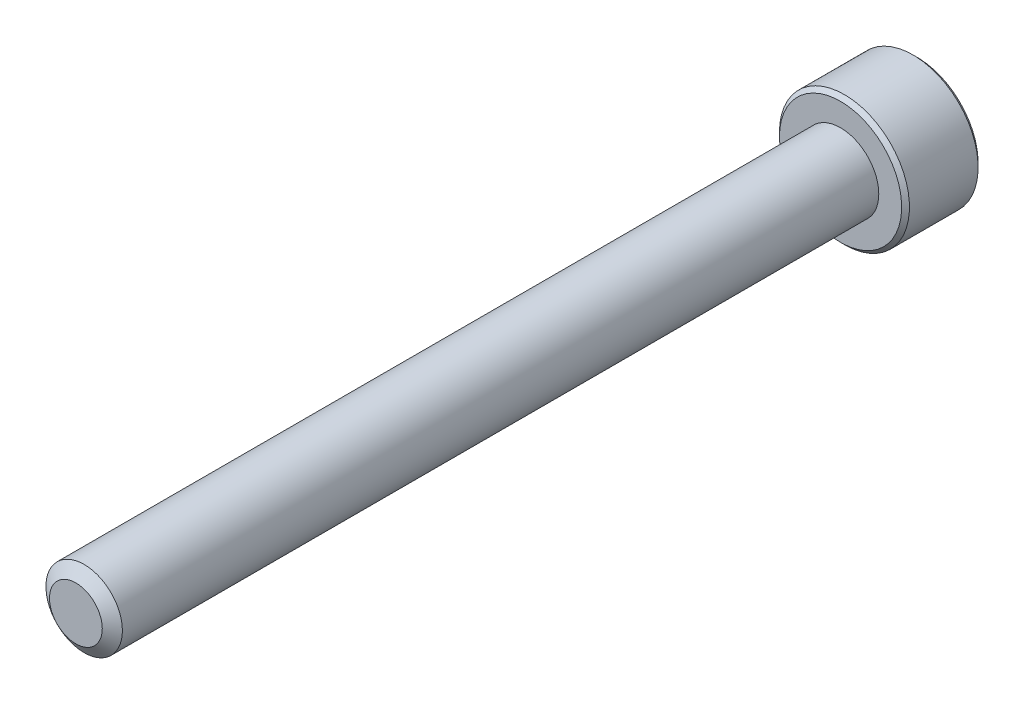
SolidWorks part; units mm, degrees
material "Alloy Steel"
ref_plane "Front Plane" through (0, 0, 0) normal (0, 0, 1) x (1, 0, 0)
ref_plane "Top Plane" through (0, 0, 0) normal (0, 1, 0) x (1, 0, 0)
ref_plane "Right Plane" through (0, 0, 0) normal (1, 0, 0) x (0, 0, -1)
sketch "Sketch1" plane through (0, 0, 0) normal (0, 0, 1) x (1, 0, 0)
  circle A0 centre (0, 0) radius 2.5
  dimension "OD" = 5
extrude "Extrude1" add sketch "Sketch1" against normal blind 50
sketch "Sketch2" plane through (0, 0, 0) normal (0, 0, 1) x (1, 0, 0)
  circle A0 centre (0, 0) radius 2.5 construction
  circle A1 centre (0, 0) radius 2.5
curve "Helix/Spiral1" [suppressed] pitch 0.8 height 50.8 turns 63.5 parameters "pitch"=0.8
sketch "Sketch3" plane through (0, 0, 0) normal (1, 0, 0) x (0, 0, -1)
  line L0 (-0.7, 2.5) -> (-0.4, 1.9804)
  line L1 (-0.4, 1.9804) -> (-0.3, 1.9804)
  line L2 (-0.3, 1.9804) -> (0, 2.5)
  line L3 (-0.7, 2.5) -> (0, 2.5)
  line L4 (-0.35, 2.5) -> (-0.35, 1.9804) construction
  line L5 (-0.55, 2.2402) -> (-0.15, 2.2402) construction
  line L6 (0, 2.5) -> (0, -2.5) construction
  line L7 (0, -2.5) -> (50, -2.5) construction
  point P11 (3.6, -2.5)
  dimension "D1" = 0.1
  dimension "D2" = 0.4
  dimension "D3" = 60
  dimension "D4" = 3.6
sweep "Cut-Sweep1" [suppressed] cut profiles "Sketch3" path "Helix/Spiral1"
sketch "Sketch4" plane through (0, 0, 0) normal (1, 0, 0) x (0, 0, -1)
  line L0 (0.5417, 2.5) -> (0, 1.7264)
  line L1 (0, 1.7264) -> (0, 2.5)
  line L2 (0.5417, 2.5) -> (0, 2.5)
  line L3 (-0.7, 2.5) -> (0, 2.5) construction
  line L4 (0, 0) -> (7.0209, 0) construction
  dimension "D1" = 55
  dimension "D2" = 0.254
revolve "Cut-Revolve1" cut sketch "Sketch4" angle 360 about L4
sketch "Sketch5" [suppressed] plane through (0, 0, 0) normal (1, 0, 0) x (0, 0, -1)
  line L0 (50, -1.7838) -> (50, 1.991) construction
  line L1 (50, 2.5) -> (22.1202, 2.5)
  line L2 (50, 2.5) -> (50, 0)
  line L3 (50, 0) -> (22, 0)
  line L4 (22, 2.1698) -> (22, 0)
  line L5 (22.1202, 2.5) -> (22, 2.1698)
  line L6 (0, 0) -> (9.9695, 0) construction
  point P3 (22, 2.5)
  point P10 (22, 2.5)
  dimension "D1" = 0.3302
  dimension "Thread min" = 22
  dimension "D3" = 20
revolve "partially thread" [suppressed] add sketch "Sketch5" angle 360 about L6
sketch "Sketch6" plane through (0, 0, -50) normal (0, 0, -1) x (-1, 0, 0)
  circle A0 centre (0, 0) radius 4.25
  dimension "head dia" = 8.5
extrude "Extrude2" add sketch "Sketch6" along normal blind 5
sketch "Sketch7" plane through (0, 0, -55) normal (0, 0, -1) x (-1, 0, 0)
  line L1 (0, 2.3094) -> (-2, 1.1547)
  line L2 (-2, 1.1547) -> (-2, -1.1547)
  line L3 (-2, -1.1547) -> (0, -2.3094)
  line L4 (0, -2.3094) -> (2, -1.1547)
  line L5 (2, -1.1547) -> (2, 1.1547)
  line L6 (2, 1.1547) -> (0, 2.3094)
  circle A0 centre (0, 0) radius 2 construction
  dimension "hex dia" = 4
extrude "Cut-Extrude1" cut sketch "Sketch7" against normal blind 3
sketch "Sketch8" plane through (0, 0, -55) normal (0, 0, -1) x (-1, 0, 0)
  circle A0 centre (0, 0) radius 2.3094
extrude "Cut-Extrude2" cut sketch "Sketch8" against normal through all draft 45
chamfer "Chamfer1" distance 0.255 angle 45 2 edges at (-4.25, 0, -55) (-4.25, 0, -50)
sketch "Sketch9" plane through (0, 0, 0) normal (1, 0, 0) x (0, 0, -1)
  line L0 (0, 2.5) -> (0, -2.5) construction
  line L1 (4.4, 2.5) -> (4.4, -2.5) construction
  dimension "D1" = 4.4
sketch "Sketch10" plane through (0, 0, 0) normal (1, 0, 0) x (0, 0, -1)
  line L0 (50, 2.5) -> (50, 0)
  line L1 (50, 2.5) -> (49.8, 2.5)
  line L2 (49.8, 2.5) -> (48.7645, 0)
  line L3 (50, 0) -> (48.7645, 0)
  line L4 (50, 3.995) -> (50, -3.995) construction
  dimension "D1" = 22.5
  dimension "D2" = 0.2
revolve "Revolve1" add sketch "Sketch10" angle 360 about L3
equation "\"D3@Helix/Spiral1\" = \"screw length@Extrude1\"+\"pitch@Helix/Spiral1\""
equation "\"D1@Sketch3\" = \"pitch@Helix/Spiral1\"*.125"
equation "\"D2@Sketch3\" = \"pitch@Helix/Spiral1\"*.5"
equation "\"D1@Cut-Extrude1\" = \"hex dia@Sketch7\"*.75"
equation "\"D1@Chamfer1\" = \"head dia@Sketch6\"*.03"
equation "\"D1@Sketch9\" = \"pitch@Helix/Spiral1\"*5.5"
equation "\"D2@Sketch10\" = \"pitch@Helix/Spiral1\"*.25"
equation "\"D4@Sketch3\" = \"pitch@Helix/Spiral1\"*4.50"
